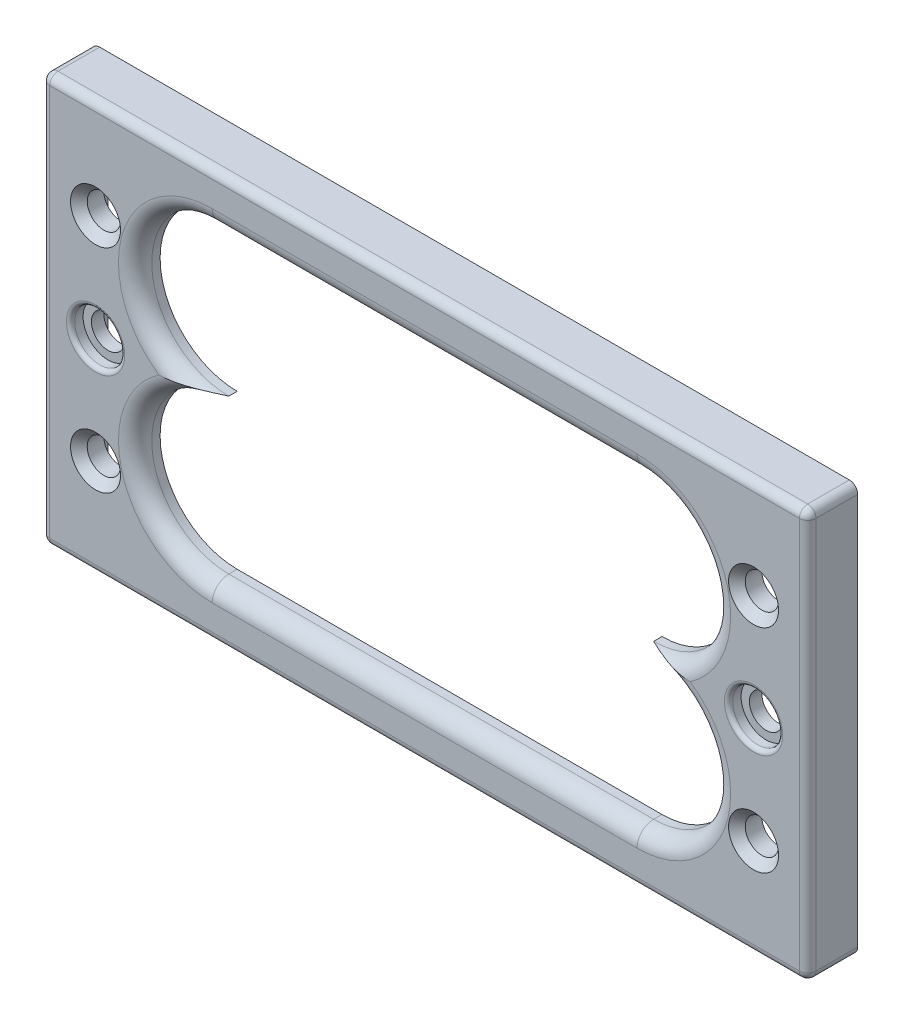
SolidWorks part; units mm, degrees
ref_plane "Front Plane" through (0, 0, 0) normal (0, 0, 1) x (1, 0, 0)
ref_plane "Top Plane" through (0, 0, 0) normal (0, 1, 0) x (1, 0, 0)
ref_plane "Right Plane" through (0, 0, 0) normal (1, 0, 0) x (0, 0, -1)
sketch "Sketch1" plane through (0, 0, 0) normal (0, 0, 1) x (1, 0, 0)
  line L0 (-25.5, 0) -> (25.5, 0) construction
  line L1 (55, 0) -> (-55, 0) construction
  line L2 (-25.5, 0) -> (25.5, 0)
  line L3 (25.5, 0) -> (25.5, -9.25) construction
  line L4 (25.5, -18.5) -> (-25.5, -18.5) construction
  line L5 (0, -55) -> (0, 55) construction
  line L6 (0, -37) -> (0, 0) construction
  line L7 (25.5, -37) -> (25.5, -27.75) construction
  line L8 (-25.5, -37) -> (25.5, -37) construction
  line L9 (-25.5, -37) -> (25.5, -37)
  line L10 (-25.5, -37) -> (-25.5, -27.75) construction
  line L11 (-25.5, 0) -> (-25.5, -9.25) construction
  line L12 (0, 0) -> (0, 6.0333) construction
  line L13 (34.75, -9.25) -> (34.75, -27.75) construction
  line L14 (34.75, -27.75) -> (34.75, -18.5) construction
  line L15 (34.75, -18.5) -> (39.5, -18.5) construction
  line L16 (-46, 6.0333) -> (46, 6.0333)
  line L17 (46, 6.0333) -> (46, -43.0333)
  line L18 (-46, -43.0333) -> (46, -43.0333)
  line L19 (-46, 6.0333) -> (-46, -43.0333)
  arc A0 (25.5, 0) -> (25.5, -18.5) centre (25.5, -9.25) cw
  arc A1 (25.5, -37) -> (25.5, -18.5) centre (25.5, -27.75) ccw
  arc A2 (-25.5, -37) -> (-25.5, -18.5) centre (-25.5, -27.75) cw
  arc A3 (-25.5, 0) -> (-25.5, -18.5) centre (-25.5, -9.25) ccw
  circle A4 centre (39.5, -18.5) radius 2
  circle A5 centre (-39.5, -18.5) radius 2
  circle A10 centre (-39.5, -5.75) radius 2
  circle A11 centre (39.5, -5.75) radius 2
  circle A12 centre (-39.5, -31.25) radius 2
  circle A13 centre (39.5, -31.25) radius 2
  point P16 (0, -18.5)
  point P29 (46, -18.5)
  point P30 (-46, -18.5)
  point P32 (0, -43.0333)
  dimension "D2" = 92
  dimension "D1" = 39.5
  dimension "D3" = 51
  dimension "D4" = 12.75
extrude "Boss-Extrude1" add sketch "Sketch1" along normal blind 3
sketch "Sketch2" plane through (0, 0, 0) normal (0, 0, -1) x (-1, 0, 0)
  line L0 (0, 6.0333) -> (0, 4.0333) construction
  line L1 (-46, 6.0333) -> (46, 6.0333) construction
  line L2 (0, 4.0333) -> (44, 4.0333)
  line L3 (44, 4.0333) -> (44, -41.0333)
  line L4 (44, -41.0333) -> (-44, -41.0333)
  line L5 (-44, -41.0333) -> (-44, 4.0333)
  line L6 (-44, 4.0333) -> (0, 4.0333)
  line L7 (46, 6.0333) -> (-46, 6.0333)
  line L8 (-46, -43.0333) -> (-46, 6.0333) construction
  line L9 (-46, 6.0333) -> (-46, -43.0333)
  line L10 (-46, -43.0333) -> (46, -43.0333)
  line L11 (46, -43.0333) -> (46, 6.0333)
  dimension "D1" = 2
  dimension "D2" = 88
  dimension "D3" = 2
  dimension "D4" = 2
  dimension "D5" = 45.0667
  dimension "D6" = 2
extrude "Boss-Extrude2" add sketch "Sketch2" along normal blind 3
fillet "Fillet1" radius 1 8 edges at (46, 6.0333, 0) (46, -43.0333, 0) (46, -18.5, 3) (-46, -18.5, 3) (0, 6.0333, 3) (-46, 6.0333, 0) (-46, -43.0333, 0) (0, -43.0333, 3)
fillet "Fillet2" radius 2 6 edges at (34.75, -9.25, 3) (0, 0, 3) (34.75, -27.75, 3) (0, -37, 3) (-34.75, -9.25, 3) (-34.75, -27.75, 3)
chamfer "Chamfer1" distance 1 angle 45 4 edges at (37.5, -5.75, 3) (-37.5, -5.75, 3) (-41.5, -31.25, 3) (41.5, -31.25, 3)
sketch "Sketch3" plane through (0, 0, 3) normal (0, 0, 1) x (1, 0, 0)
  line L0 (0, 5.0333) -> (0, 2) construction
  line L1 (45, 5.0333) -> (-45, 5.0333) construction
  line L2 (-25.5, 2) -> (25.5, 2) construction
  circle A0 centre (-39.5, -18.5) radius 3
  circle A1 centre (39.5, -18.5) radius 3
  dimension "D1" = 6
extrude "Cut-Extrude1" cut sketch "Sketch3" against normal blind 1.5
fillet "Fillet3" radius 0.5 2 edges at (36.5, -18.5, 3) (-36.5, -18.5, 3)
